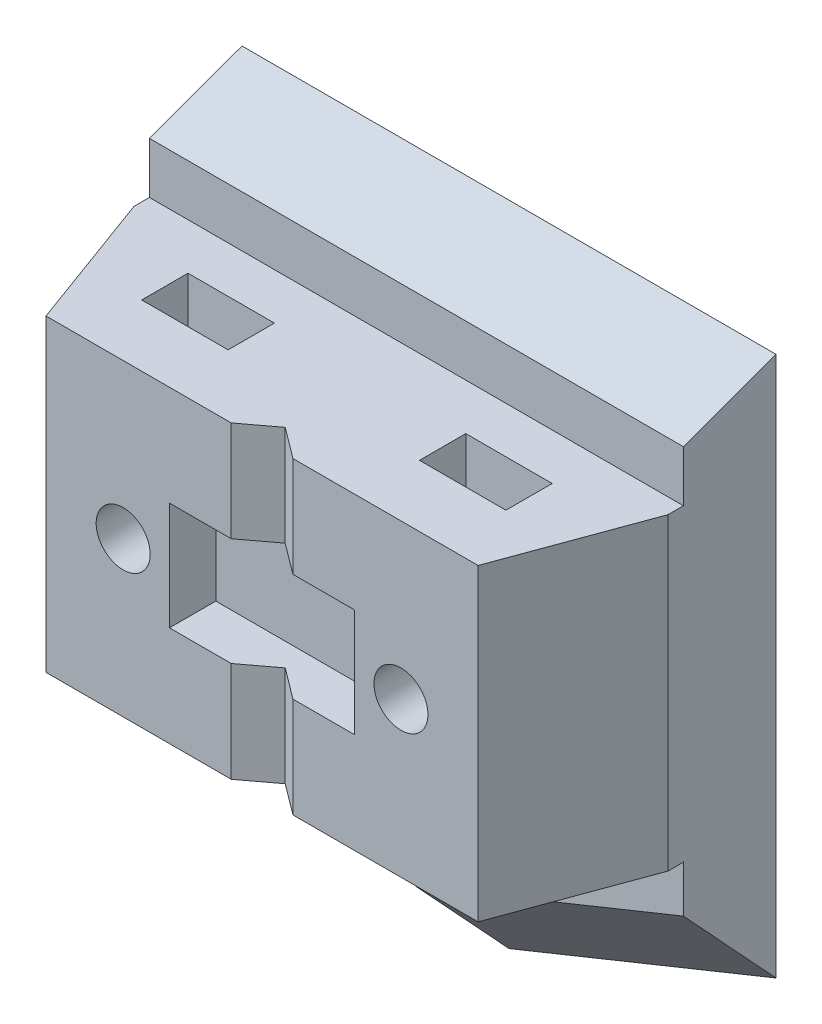
SolidWorks part; units mm, degrees
ref_plane "Plano frontal" through (0, 0, 0) normal (0, 0, 1) x (1, 0, 0)
ref_plane "Plano superior" through (0, 0, 0) normal (0, 1, 0) x (1, 0, 0)
ref_plane "Plano direito" through (0, 0, 0) normal (1, 0, 0) x (0, 0, -1)
sketch "Esboço1" plane through (0, 0, 0) normal (0, 0, 1) x (1, 0, 0)
  line L1 (-17.3, 13) -> (17.3, 13)
  line L2 (-17.3, 13) -> (-17.3, -13)
  line L3 (-17.3, -13) -> (17.3, -13)
  line L4 (17.3, 13) -> (17.3, -13)
  line L5 (-17.3, 13) -> (17.3, -13) construction
  line L6 (-17.3, -13) -> (17.3, 13) construction
  point P0 (0, 0)
  dimension "D1" = 34.6
  dimension "D2" = 26
extrude "Ressalto-extrusão1" add sketch "Esboço1" along normal blind 7
sketch "Esboço10" plane through (0, 0, 0) normal (0, 0, -1) x (-1, 0, 0)
  line L0 (-17.3, -19.5) -> (0, -26.5)
  line L1 (-17.3, 13) -> (17.3, 13)
  line L2 (-17.3, 13) -> (-17.3, 15.5)
  line L3 (-17.3, 15.5) -> (17.3, 15.5)
  line L4 (17.3, 13) -> (17.3, 15.5)
  line L5 (0, -26.5) -> (17.3, -19.5)
  line L6 (-17.3, -19.5) -> (-17.3, -13)
  line L7 (-17.3, -13) -> (17.3, -13)
  line L8 (17.3, -13) -> (17.3, -19.5)
  dimension "D1" = 7
  dimension "D2" = 35
  dimension "D3" = 2.5
extrude "Ressalto-extrusão4" add sketch "Esboço10" against normal up to surface (7 mm away) up to face at (0, 0, 7)
chamfer "Chanfro1" distance 7 angle 45 2 edges at (8.65, -23, 7) (-8.65, -23, 7)
chamfer "Chanfro2" distance 7 angle 20 1 edges at (0, 15.5, 7) first distance on face at (0, 15.5, 3.5)
sketch "Esboço11" plane through (0, 0, 0) normal (0, 1, 0) x (1, 0, 0)
  line L0 (-17.3, -7) -> (-14, -16)
  line L1 (17.3, -7) -> (-17.3, -7) construction
  line L2 (-14, -16) -> (-2, -16)
  line L3 (-17.3, -7) -> (17.3, -7)
  line L4 (0, 0) -> (0, -18.2406) construction
  line L5 (-17.3, 0) -> (17.3, 0) construction
  line L6 (17.3, -7) -> (14, -16)
  line L7 (2, -16) -> (14, -16)
  line L8 (11.8, -12) -> (6.2, -9) construction
  line L9 (-11.8, -9) -> (-6.2, -9)
  line L10 (-11.8, -9) -> (-11.8, -12)
  line L11 (-11.8, -12) -> (-6.2, -12)
  line L12 (-6.2, -9) -> (-6.2, -12)
  line L13 (-11.8, -9) -> (-6.2, -12) construction
  line L14 (-11.8, -12) -> (-6.2, -9) construction
  line L15 (11.8, -9) -> (6.2, -12) construction
  line L16 (6.2, -9) -> (6.2, -12)
  line L17 (11.8, -12) -> (6.2, -12)
  line L18 (11.8, -9) -> (11.8, -12)
  line L19 (11.8, -9) -> (6.2, -9)
  line L20 (-2, -16) -> (0, -14.5)
  line L21 (0, -14.5) -> (2, -16)
  circle A0 centre (0, -16.375) radius 1.5 construction
  point P12 (0, -7)
  point P13 (0, -16.2024)
  point P14 (-9, -10.5)
  point P31 (9, -10.5)
  dimension "D2" = 1.5
  dimension "D3" = 4
  dimension "D9" = 3
  dimension "D1" = 9
  dimension "D4" = 5.6
  dimension "D5" = 3
  dimension "D6" = 18
  dimension "D7" = 2
  dimension "D8" = 28
extrude "Ressalto-extrusão5" add sketch "Esboço11" along normal mid plane 20
sketch "Esboço12" plane through (0, 0, 16) normal (0, 0, 1) x (1, 0, 0)
  line L0 (0, 0) -> (0, 7.5857) construction
  circle A0 centre (-9, 0) radius 1.75
  circle A1 centre (9, 0) radius 1.75
  dimension "D2" = 3.5
  dimension "D1" = 18
extrude "Corte-extrusão1" cut sketch "Esboço12" against normal blind 20
sketch "Esboço13" plane through (0, 0, 7) normal (0, 0, 1) x (1, 0, 0)
  line L0 (17.3, -11.9487) -> (17.3, -10) construction
  line L1 (-17.3, 10) -> (17.3, 10)
  line L2 (-17.3, 10) -> (-17.3, 15.5)
  line L3 (-17.3, 15.5) -> (17.3, 15.5)
  line L4 (17.3, 10) -> (17.3, 15.5)
  line L5 (-17.3, -10) -> (17.3, -10)
  line L6 (-17.3, -10) -> (-17.3, -28.3931)
  line L7 (-17.3, -28.3931) -> (17.3, -28.3931)
  line L8 (17.3, -10) -> (17.3, -28.3931)
extrude "Corte-extrusão2" cut sketch "Esboço13" against normal blind 1
sketch "Esboço14" plane through (0, 0, 16) normal (0, 0, 1) x (1, 0, 0)
  line L1 (-6, 3.5) -> (6, 3.5)
  line L2 (-6, 3.5) -> (-6, -3.5)
  line L3 (-6, -3.5) -> (6, -3.5)
  line L4 (6, 3.5) -> (6, -3.5)
  line L5 (-6, 3.5) -> (6, -3.5) construction
  line L6 (-6, -3.5) -> (6, 3.5) construction
  point P0 (0, 0)
  dimension "D1" = 12
  dimension "D2" = 7
extrude "Corte-extrusão3" cut sketch "Esboço14" against normal blind 3
